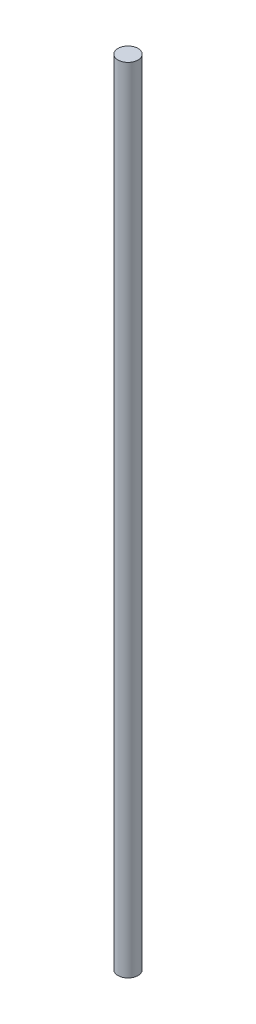
SolidWorks part; units mm, degrees
ref_plane "Front Plane" through (0, 0, 0) normal (0, 0, 1) x (1, 0, 0)
ref_plane "Top Plane" through (0, 0, 0) normal (0, 1, 0) x (1, 0, 0)
ref_plane "Right Plane" through (0, 0, 0) normal (1, 0, 0) x (0, 0, -1)
sketch "Sketch1" plane through (0, 0, 0) normal (0, 1, 0) x (1, 0, 0)
  circle A0 centre (0, 0) radius 3
  dimension "D1" = 6
extrude "Boss-Extrude1" add sketch "Sketch1" along normal blind 236.982
